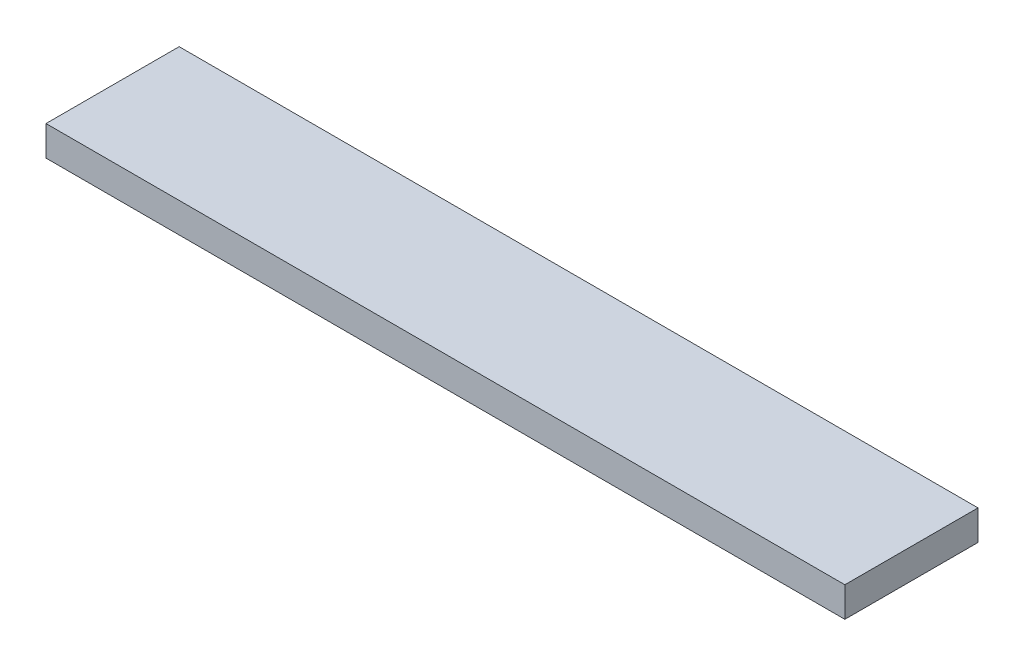
SolidWorks part; units mm, degrees
ref_plane "Front Plane" through (0, 0, 0) normal (0, 0, 1) x (1, 0, 0)
ref_plane "Top Plane" through (0, 0, 0) normal (0, 1, 0) x (1, 0, 0)
ref_plane "Right Plane" through (0, 0, 0) normal (1, 0, 0) x (0, 0, -1)
sketch "Sketch1" plane through (0, 0, 0) normal (0, 1, 0) x (1, 0, 0)
  line L1 (0, 0) -> (120, 0)
  line L2 (0, 0) -> (0, 20)
  line L3 (0, 20) -> (120, 20)
  line L4 (120, 0) -> (120, 20)
  dimension "D1" = 20
  dimension "D2" = 120
extrude "Boss-Extrude1" add sketch "Sketch1" along normal blind 4.5
